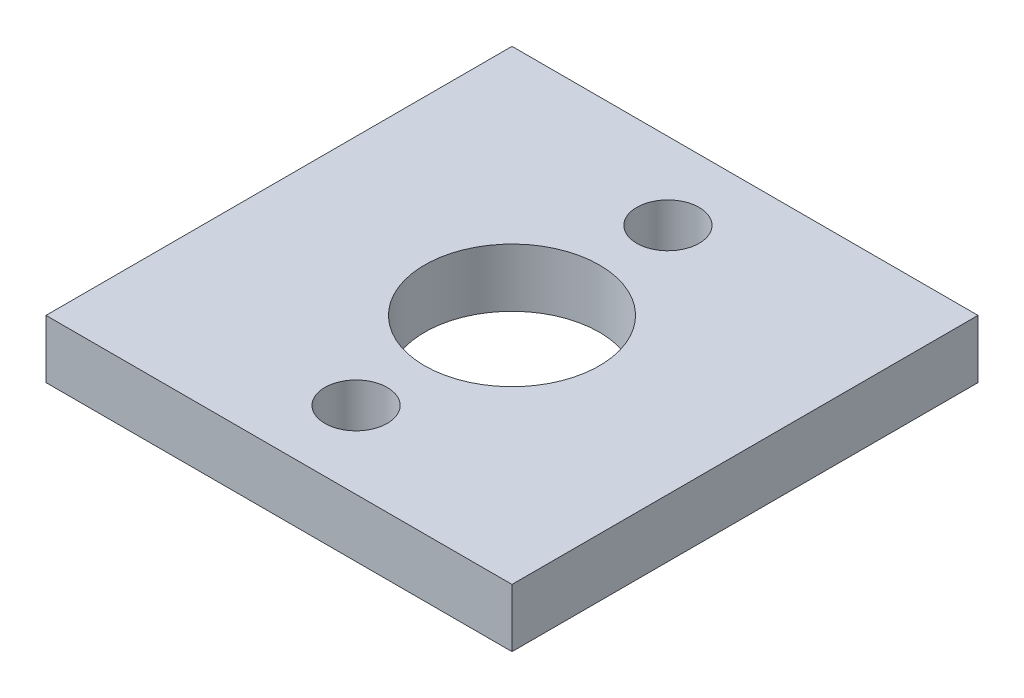
SolidWorks part; units mm, degrees
ref_plane "Front Plane" through (0, 0, 0) normal (0, 0, 1) x (1, 0, 0)
ref_plane "Top Plane" through (0, 0, 0) normal (0, 1, 0) x (1, 0, 0)
ref_plane "Right Plane" through (0, 0, 0) normal (1, 0, 0) x (0, 0, -1)
sketch "Sketch2" plane through (0, 0, 0) normal (0, 1, 0) x (1, 0, 0)
  line L1 (-12.7, -12.7) -> (12.7, -12.7)
  line L2 (-12.7, -12.7) -> (-12.7, 12.7)
  line L3 (-12.7, 12.7) -> (12.7, 12.7)
  line L4 (12.7, -12.7) -> (12.7, 12.7)
  line L5 (-12.7, -12.7) -> (12.7, 12.7) construction
  line L6 (-12.7, 12.7) -> (12.7, -12.7) construction
  point P0 (0, 0)
  dimension "D2" = 25.4
extrude "Boss-Extrude1" add sketch "Sketch2" along normal blind 3.175
sketch "Sketch4" plane through (0, 3.175, 0) normal (0, 1, 0) x (1, 0, 0)
  line L0 (0, 8.5) -> (0, -8.5) construction
  circle A0 centre (0, 0) radius 4.7625
  dimension "D3" = 9.525
  dimension "D1" = 17
extrude "Cut-Extrude1" cut sketch "Sketch4" against normal through all
hole_wizard "M3 Clearance Hole2" positions "3DSketch5" profile "Sketch9" hole size "M3" standard "ANSI Metric" end condition through all
sketch3d "3DSketch5"
  point P0 (0, 3.175, -8.5)
  point P3 (0, 3.175, 8.5)
sketch "Sketch9" plane through (0, 3.175, -8.5) normal (1, 0, 0) x (0, 0, 1)
  line L0 (0, 0) -> (0, 3.175)
  line L1 (0, 3.175) -> (1.7, 3.175)
  line L2 (1.7, 3.175) -> (1.7, 0)
  line L5 (1.7, 0) -> (0, 0)
  line L11 (0, -6.35) -> (0, 107.95) construction
  dimension "Thru Hole Dia." = 3.4
  dimension "Thru Hole Depth" = 3.175
